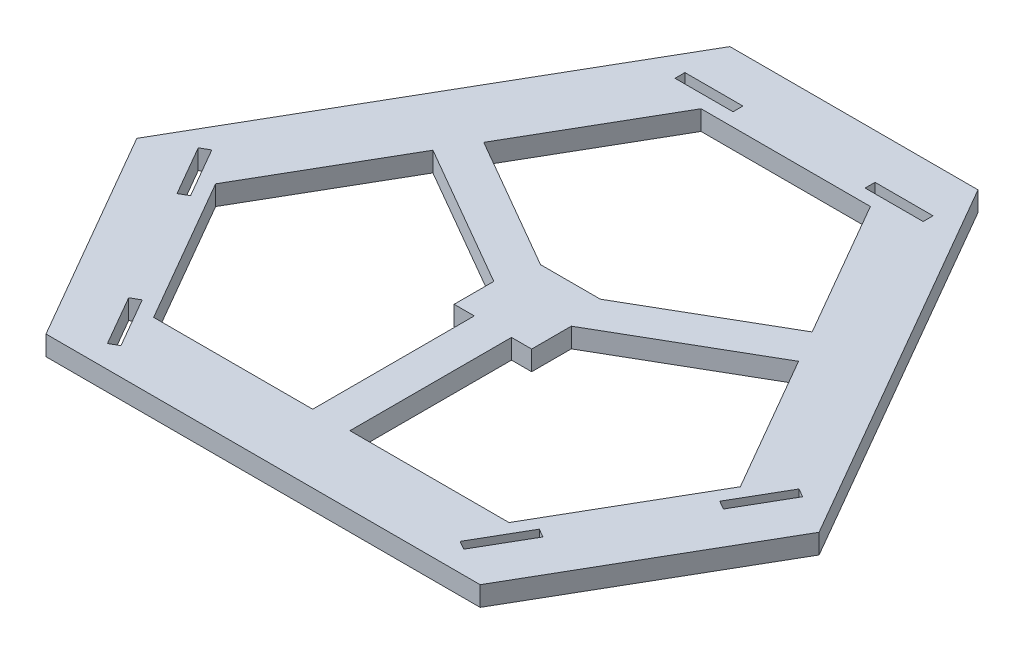
SolidWorks part; units mm, degrees
ref_plane "Front Plane" through (0, 0, 0) normal (0, 0, 1) x (1, 0, 0)
ref_plane "Top Plane" through (0, 0, 0) normal (0, 1, 0) x (1, 0, 0)
ref_plane "Right Plane" through (0, 0, 0) normal (1, 0, 0) x (0, 0, -1)
sketch "Sketch1" plane through (0, 0, 0) normal (0, 1, 0) x (1, 0, 0)
  line L0 (70, -86.6025) -> (110, -17.3205)
  line L1 (110, -17.3205) -> (40, 103.923)
  line L2 (-40, 103.923) -> (-110, -17.3205)
  line L3 (-70, -86.6025) -> (70, -86.6025)
  line L4 (-110, -17.3205) -> (-70, -86.6025)
  line L5 (-40, 103.923) -> (40, 103.923)
  line L6 (0, 103.923) -> (0, -86.6025) construction
  line L7 (90, -51.9615) -> (-75, 43.3013) construction
  line L8 (-110, -17.3205) -> (-88.4498, -4.8785) construction
  line L9 (-90, -51.9615) -> (0, 0) construction
  line L10 (-100.65, -33.5152) -> (-79.0998, -21.0731) construction
  line L11 (-94.6714, -8.4705) -> (-85.3214, -24.6652)
  line L12 (-85.3214, -24.6652) -> (-88.0926, -26.2652)
  line L13 (-88.0926, -26.2652) -> (-97.4426, -10.0705)
  line L14 (-97.4426, -10.0705) -> (-94.6714, -8.4705)
  line L16 (-57.4426, -79.3525) -> (-54.6714, -77.7525)
  line L17 (-66.7926, -63.1579) -> (-57.4426, -79.3525)
  line L18 (-64.0214, -61.5579) -> (-66.7926, -63.1579)
  line L19 (-54.6714, -77.7525) -> (-64.0214, -61.5579)
  line L20 (54.6714, -77.7525) -> (64.0214, -61.5579)
  line L21 (64.0214, -61.5579) -> (66.7926, -63.1579)
  line L22 (66.7926, -63.1579) -> (57.4426, -79.3525)
  line L23 (57.4426, -79.3525) -> (54.6714, -77.7525)
  line L24 (97.4426, -10.0705) -> (94.6714, -8.4705)
  line L25 (88.0926, -26.2652) -> (97.4426, -10.0705)
  line L26 (85.3214, -24.6652) -> (88.0926, -26.2652)
  line L27 (94.6714, -8.4705) -> (85.3214, -24.6652)
  line L28 (40, 86.223) -> (21.3, 86.223)
  line L29 (21.3, 86.223) -> (21.3, 89.423)
  line L30 (21.3, 89.423) -> (40, 89.423)
  line L31 (40, 89.423) -> (40, 86.223)
  line L32 (-40, 89.423) -> (-40, 86.223)
  line L33 (-21.3, 89.423) -> (-40, 89.423)
  line L34 (-21.3, 86.223) -> (-21.3, 89.423)
  line L35 (-40, 86.223) -> (-21.3, 86.223)
  circle A0 centre (0, 0) radius 86.6025 construction
  point P13 (-105.325, -25.4178)
  point P35 (105.325, -25.4178)
  dimension "D1" = 140
  dimension "D2" = 80
  dimension "D3" = 9.35
  dimension "D4" = 18.7
  dimension "D5" = 9.35
  dimension "D6" = 3.2
  dimension "D7" = 14.5
extrude "Boss-Extrude1" add sketch "Sketch1" along normal blind 6.35
sketch "Sketch2" plane through (0, 6.35, 0) normal (0, 1, 0) x (1, 0, 0)
  line L0 (-84.5966, -17.3205) -> (-27.2983, 81.923)
  line L1 (-27.2983, 81.923) -> (27.2983, 81.923)
  line L2 (27.2983, 81.923) -> (84.5966, -17.3205)
  line L3 (84.5966, -17.3205) -> (57.2983, -64.6025)
  line L4 (57.2983, -64.6025) -> (-57.2983, -64.6025)
  line L5 (-57.2983, -64.6025) -> (-84.5966, -17.3205)
  line L6 (-110, -17.3205) -> (-70, -86.6025) construction
  line L7 (-40, 103.923) -> (-110, -17.3205) construction
  line L8 (40, 103.923) -> (-40, 103.923) construction
  line L9 (110, -17.3205) -> (40, 103.923) construction
  line L10 (70, -86.6025) -> (110, -17.3205) construction
  line L11 (-70, -86.6025) -> (70, -86.6025) construction
  dimension "D1" = 22
  dimension "D2" = 22
  dimension "D3" = 22
  dimension "D4" = 22
  dimension "D5" = 22
  dimension "D6" = 22
extrude "Cut-Extrude1" cut sketch "Sketch2" against normal up to surface (6.35 mm away) up to face at (30.65, 0, -87.823)
sketch "Sketch3" plane through (0, 6.35, 0) normal (0, 1, 0) x (1, 0, 0)
  line L0 (-57.2983, -64.6025) -> (57.2983, -64.6025) construction
  line L1 (-6, -64.6025) -> (6, -64.6025)
  line L2 (-6, -64.6025) -> (-6, 0)
  line L3 (-6, 0) -> (6, 0)
  line L4 (6, -64.6025) -> (6, 0)
  line L5 (70.9474, -40.9615) -> (-55.9474, 32.3013) construction
  line L6 (57.2983, -64.6025) -> (84.5966, -17.3205) construction
  line L7 (-27.2983, 81.923) -> (-84.5966, -17.3205) construction
  line L8 (-70.9474, -40.9615) -> (55.9474, 32.3013) construction
  line L9 (-84.5966, -17.3205) -> (-57.2983, -64.6025) construction
  line L10 (84.5966, -17.3205) -> (27.2983, 81.923) construction
  line L11 (58.9474, 27.1051) -> (3, -5.1962)
  line L12 (-3, 5.1962) -> (3, -5.1962)
  line L13 (52.9474, 37.4974) -> (-3, 5.1962)
  line L14 (52.9474, 37.4974) -> (58.9474, 27.1051)
  line L15 (-52.9474, 37.4974) -> (3, 5.1962)
  line L16 (-3, -5.1962) -> (3, 5.1962)
  line L17 (-58.9474, 27.1051) -> (-3, -5.1962)
  line L18 (-58.9474, 27.1051) -> (-52.9474, 37.4974)
  point P6 (0, 0)
  point P28 (-6, -32.3013)
  line M4 (-84.5966, -17.3205) -> (-27.2983, 81.923)
  line M6 (27.2983, 81.923) -> (84.5966, -17.3205)
  line M8 (57.2983, -64.6025) -> (-57.2983, -64.6025)
  dimension "D1" = 12
extrude "Boss-Extrude2" add sketch "Sketch3" against normal up to surface (6.35 mm away) contours L17 L2 L4 L11 L12 L16 M8 | L16 L3 L4 L11 L13 L15 M6 | L17 L2 L3 L12 L13 L15 M4 | L12 L16 L15 L13 | L3 L12 L11 L4 | L2 L17 L16 L3 region at (0, 6.35, 34.017) region at (-29.4596, 6.35, -17.0085) region at (-3.5, 6.35, 2.0207) region at (3.5, 6.35, 2.0207) region at (29.4596, 6.35, -17.0085) region at (0, 6.35, -4.0415) up to face at (0, 0, 0)
sketch "Sketch4" plane through (0, 6.35, 0) normal (0, 1, 0) x (1, 0, 0)
  line L1 (-12.5, 12.5) -> (12.5, 12.5)
  line L2 (-12.5, 12.5) -> (-12.5, -12.5)
  line L3 (-12.5, -12.5) -> (12.5, -12.5)
  line L4 (12.5, 12.5) -> (12.5, -12.5)
  line L5 (-12.5, 12.5) -> (12.5, -12.5) construction
  line L6 (-12.5, -12.5) -> (12.5, 12.5) construction
  point P0 (0, 0)
  dimension "D1" = 25
  dimension "D2" = 25
extrude "Boss-Extrude3" add sketch "Sketch4" against normal up to surface (6.35 mm away) up to face at (-42.5685, 0, 24.5769)
equation "\"D5@Sketch1\"=\"D4@Sketch1\"/2"
equation "\"D3@Sketch1\"=\"D5@Sketch1\""
equation "\"D2@Sketch2\"=\"D1@Sketch2\""
equation "\"D3@Sketch2\"=\"D1@Sketch2\""
equation "\"D4@Sketch2\"=\"D1@Sketch2\""
equation "\"D5@Sketch2\"=\"D1@Sketch2\""
equation "\"D6@Sketch2\"=\"D1@Sketch2\""
